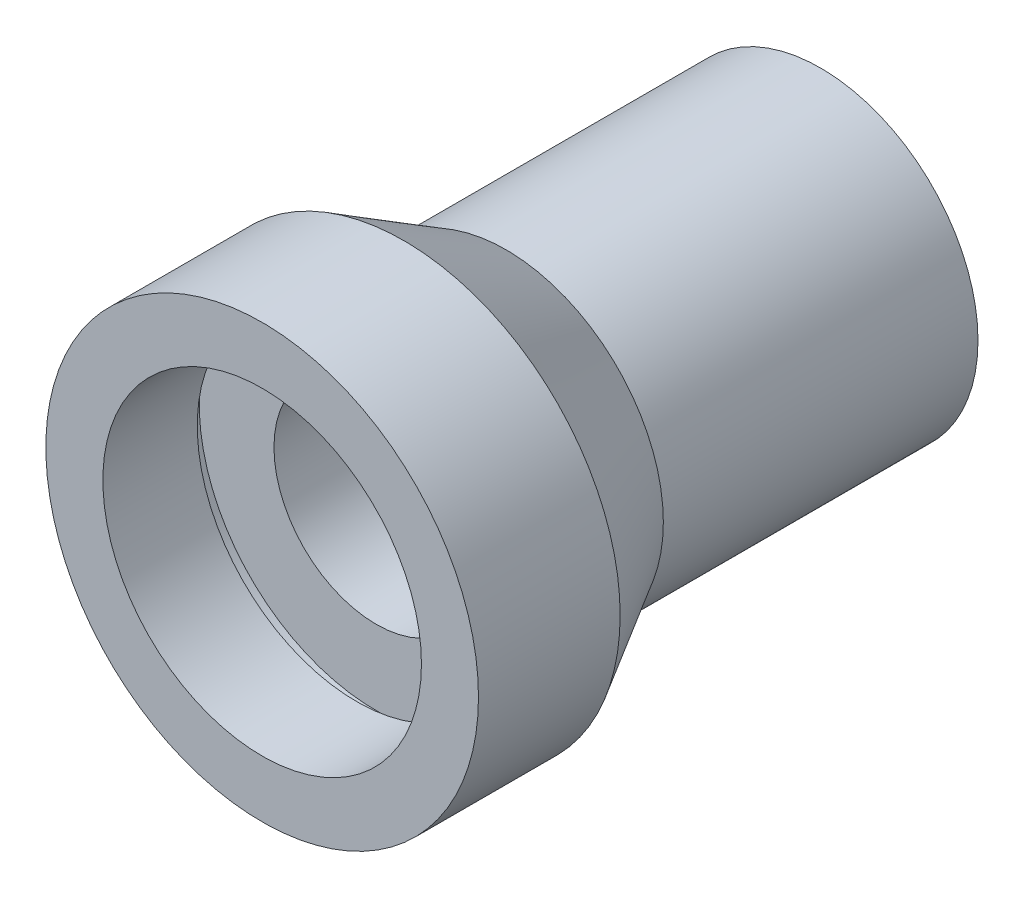
SolidWorks part; units mm, degrees
ref_plane "Front Plane" through (0, 0, 0) normal (0, 0, 1) x (1, 0, 0)
ref_plane "Top Plane" through (0, 0, 0) normal (0, 1, 0) x (1, 0, 0)
ref_plane "Right Plane" through (0, 0, 0) normal (1, 0, 0) x (0, 0, -1)
sketch "Sketch1" plane through (0, 0, 0) normal (0, 0, 1) x (1, 0, 0)
  circle A0 centre (0, 0) radius 2.6
  circle A1 centre (0, 0) radius 4
  dimension "D1" = 5.2
  dimension "D2" = 8
extrude "Boss-Extrude1" add sketch "Sketch1" along normal blind 1 and the other way blind 10
sketch "Sketch2" plane through (0, 0, 1) normal (0, 0, 1) x (1, 0, 0)
  circle A0 centre (0, 0) radius 5.5
  dimension "D1" = 11
extrude "Boss-Extrude2" add sketch "Sketch2" along normal blind 3.2
sketch "Sketch3" plane through (0, 0, 4.2) normal (0, 0, 1) x (1, 0, 0)
  circle A0 centre (0, 0) radius 4.05
  dimension "D1" = 8.1
extrude "Cut-Extrude1" cut sketch "Sketch3" against normal blind 2.9
sketch "Sketch4" plane through (0, 0, -10) normal (0, 0, -1) x (-1, 0, 0)
  circle A1 centre (0, 0) radius 2.6 construction
  circle A2 centre (0, 0) radius 2.6
extrude "Cut-Extrude2" cut sketch "Sketch4" against normal through all
sketch "Sketch5" plane through (0, 0, 1.3) normal (0, 0, 1) x (1, 0, 0)
  circle A0 centre (0, 0) radius 4.5
  dimension "D1" = 9
extrude "Cut-Extrude3" cut sketch "Sketch5" along normal blind 0.5
chamfer "Chamfer1" distance 3 angle 30 1 edges at (4, 0, 1) first distance on face at (4, 0, -10)
